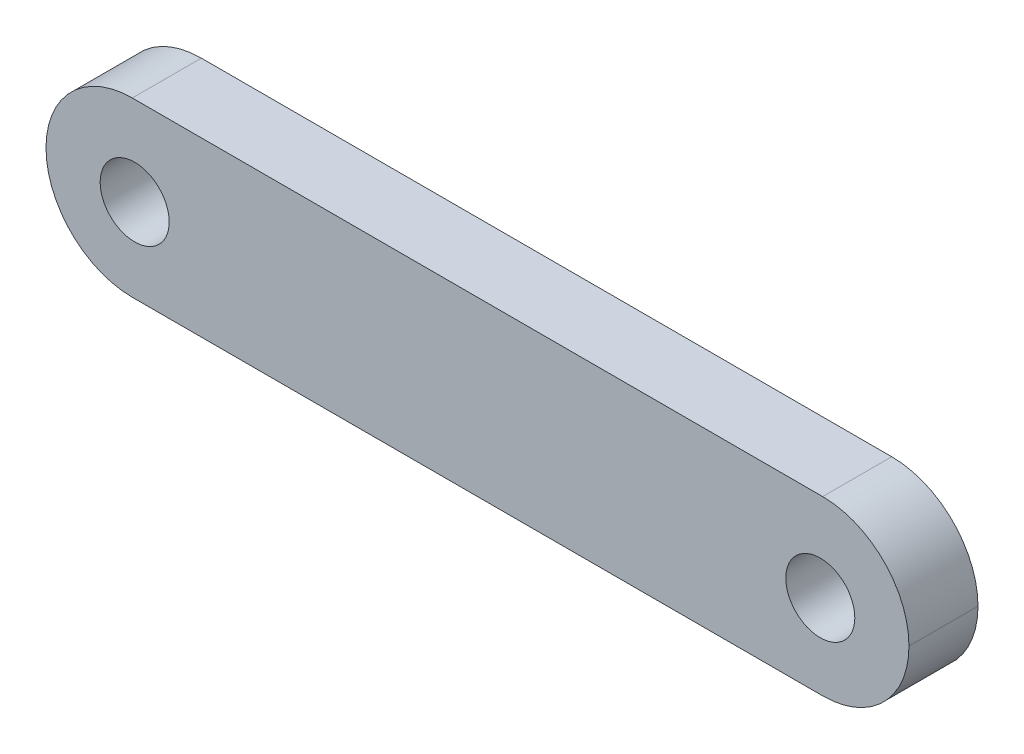
SolidWorks part; units mm, degrees
ref_plane "Front Plane" through (0, 0, 0) normal (0, 0, 1) x (1, 0, 0)
ref_plane "Top Plane" through (0, 0, 0) normal (0, 1, 0) x (1, 0, 0)
ref_plane "Right Plane" through (0, 0, 0) normal (1, 0, 0) x (0, 0, -1)
sketch "Sketch1" plane through (0, 0, 0) normal (0, 0, 1) x (1, 0, 0)
  line L0 (0, 7.3211) -> (0, -7.6539) construction
  line L1 (-12.5, 2.5) -> (12.5, 2.5)
  line L2 (-12.5, 2.5) -> (-12.5, -2.5)
  line L3 (-12.5, -2.5) -> (12.5, -2.5)
  line L4 (12.5, 2.5) -> (12.5, -2.5)
  line L5 (-12.5, 2.5) -> (12.5, -2.5) construction
  line L6 (-12.5, -2.5) -> (12.5, 2.5) construction
  circle A0 centre (9.931, -0.0768) radius 1
  circle A1 centre (-9.931, -0.0768) radius 1
  point P0 (0, 0)
  point P12 (0, 0)
  point P13 (-5.415, 0)
  point P14 (7.5, 2.5)
  dimension "D1" = 12.5
  dimension "D2" = 5
extrude "Boss-Extrude1" add sketch "Sketch1" along normal blind 2
fillet "Fillet1" radius 2.5 4 edges at (-12.5, -2.5, 1) (-12.5, 2.5, 1) (12.5, -2.5, 1) (12.5, 2.5, 1)
